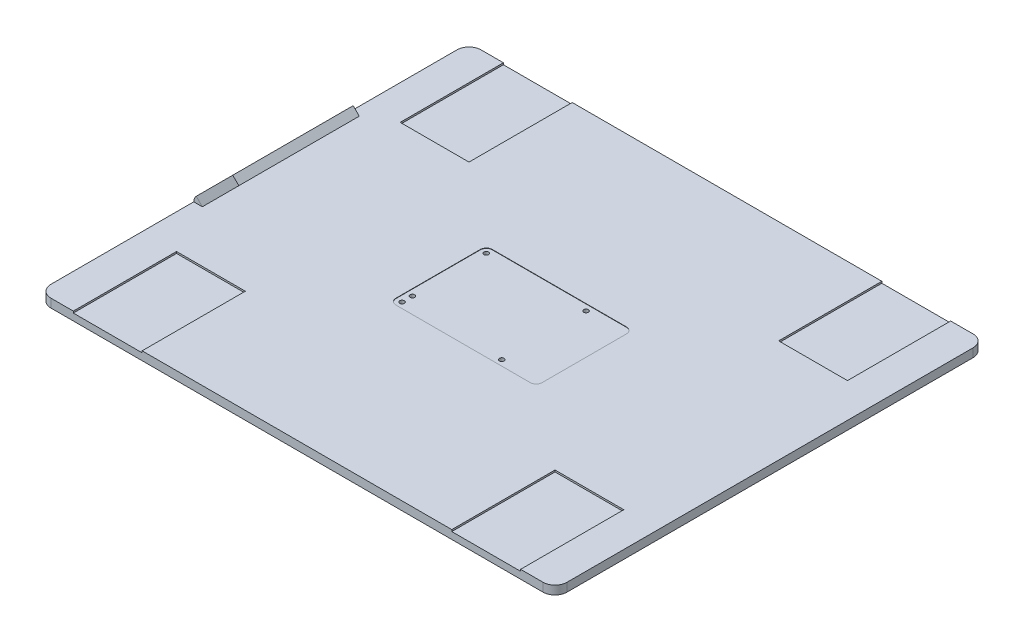
SolidWorks part; units mm, degrees
ref_plane "Front Plane" through (0, 0, 0) normal (0, 0, 1) x (1, 0, 0)
ref_plane "Top Plane" through (0, 0, 0) normal (0, 1, 0) x (1, 0, 0)
ref_plane "Right Plane" through (0, 0, 0) normal (1, 0, 0) x (0, 0, -1)
sketch "Sketch1" plane through (0, 0, 0) normal (0, 1, 0) x (1, 0, 0)
  line L0 (107.2728, -97.2075) -> (107.2728, -100.7075) construction
  line L1 (7, 0) -> (293, 0)
  line L2 (0, -7) -> (0, -243)
  line L3 (7, -250) -> (293, -250)
  line L4 (300, -7) -> (300, -243)
  line L5 (110.7728, -97.2075) -> (188.7728, -97.2075)
  line L6 (107.2728, -100.7075) -> (107.2728, -149.7075)
  line L7 (110.7728, -153.2075) -> (188.7728, -153.2075)
  line L8 (192.2728, -100.7075) -> (192.2728, -149.7075)
  line L9 (107.2728, -100.7075) -> (107.2728, -149.7075)
  line L10 (107.2728, -100.7075) -> (192.2728, -100.7075) construction
  line L11 (107.2728, -149.7075) -> (192.2728, -149.7075) construction
  line L12 (107.2728, -97.2075) -> (110.7728, -97.2075) construction
  line L13 (110.7728, -97.2075) -> (110.7728, -153.2075) construction
  line L14 (110.7728, -97.2075) -> (168.7728, -97.2075) construction
  line L15 (168.7728, -97.2075) -> (168.7728, -153.2075) construction
  line L16 (110.7728, -97.2075) -> (110.7728, -100.7075) construction
  line L17 (110.7728, -100.7075) -> (168.7728, -100.7075) construction
  line L18 (168.7728, -100.7075) -> (168.7728, -149.7075) construction
  line L19 (168.7728, -149.7075) -> (110.7728, -149.7075) construction
  line L20 (110.7728, -149.7075) -> (110.7728, -100.7075) construction
  line L21 (110.7728, -149.7075) -> (110.7728, -143.7075) construction
  line L22 (150, 0) -> (150, -250) construction
  line L23 (0, -125) -> (300, -125) construction
  line L24 (300, 0) -> (280, 0) construction
  line L25 (20, 0) -> (60, 0)
  line L26 (20, 0) -> (20, -60)
  line L27 (20, -60) -> (60, -60)
  line L28 (60, 0) -> (60, -60)
  line L29 (0, -250) -> (20, -250) construction
  line L30 (280, 0) -> (240, 0)
  line L31 (280, 0) -> (280, -60)
  line L32 (280, -60) -> (240, -60)
  line L33 (240, 0) -> (240, -60)
  line L34 (300, -250) -> (280, -250) construction
  line L36 (20, -250) -> (60, -250)
  line L37 (20, -250) -> (20, -190)
  line L38 (20, -190) -> (60, -190)
  line L39 (60, -250) -> (60, -190)
  line L40 (280, -250) -> (240, -250)
  line L41 (280, -250) -> (280, -190)
  line L42 (280, -190) -> (240, -190)
  line L43 (240, -250) -> (240, -190)
  circle A0 centre (110.7728, -100.7075) radius 1.35
  circle A1 centre (168.7728, -100.7075) radius 1.35
  circle A2 centre (168.7728, -149.7075) radius 1.35
  circle A3 centre (110.7728, -149.7075) radius 1.35
  arc A4 (110.7728, -97.2075) -> (107.2728, -100.7075) centre (110.7728, -100.7075) ccw
  arc A5 (107.2728, -149.7075) -> (110.7728, -153.2075) centre (110.7728, -149.7075) ccw
  arc A6 (188.7728, -153.2075) -> (192.2728, -149.7075) centre (188.7728, -149.7075) ccw
  arc A7 (188.7728, -97.2075) -> (192.2728, -100.7075) centre (188.7728, -100.7075) cw
  circle A8 centre (110.7728, -143.7075) radius 1.35
  arc A9 (0, -243) -> (7, -250) centre (7, -243) ccw
  arc A10 (293, -250) -> (300, -243) centre (293, -243) ccw
  arc A11 (293, 0) -> (300, -7) centre (293, -7) cw
  arc A12 (7, 0) -> (0, -7) centre (7, -7) ccw
  point P30 (107.2728, -153.2075)
  point P33 (192.2728, -153.2075)
  point P36 (192.2728, -97.2075)
  point P71 (0, 0)
  dimension "D10" = 2.7
  dimension "D11" = 2.7
  dimension "D12" = 2.7
  dimension "D13" = 2.7
  dimension "D14" = 3.5
  dimension "D15" = 3.5
  dimension "D16" = 2.7
  dimension "D21" = 7
  dimension "D1" = 300
  dimension "D2" = 250
  dimension "D3" = 85
  dimension "D4" = 56
  dimension "D5" = 3.5
  dimension "D6" = 49
  dimension "D7" = 3.5
  dimension "D8" = 3.5
  dimension "D9" = 58
  dimension "D17" = 6
  dimension "D18" = 20
  dimension "D19" = 60
  dimension "D20" = 40
extrude "Boss-Extrude1" add sketch "Sketch1" along normal blind 5 contours L4 L1 L2 L3 L5 A7 L8 A6 L7 A5 L6 A4 region at (13.5, 0, 3.9051)
extrude "Boss-Extrude2" add sketch "Sketch1<3>" along normal blind 4.8 contours A7 L5 A4 L6 A5 L7 A6 L8 A8 A3 A2 A1 A0 region at (149.8686, 0, 125.1851)
sketch "Sketch1<3>" plane through (0, 0, 0) normal (0, 1, 0) x (1, 0, 0) same geometry as "Sketch1"
extrude "Boss-Extrude3" add sketch "Sketch1<4>" along normal blind 4 contours L28 L1 L26 L27 | L1 L33 L32 L31 | L43 L3 L41 L42 | L3 L39 L38 L37 region at (40, 0, 30) region at (260, 0, 30) region at (40, 0, 220) region at (260, 0, 220)
sketch "Sketch1<4>" plane through (0, 0, 0) normal (0, 1, 0) x (1, 0, 0) same geometry as "Sketch1"
sketch "Sketch3" plane through (0, 5, 0) normal (0, 1, 0) x (1, 0, 0)
  line L0 (0, -125) -> (29.9772, -125) construction
  line L1 (0, -7) -> (0, -243) construction
  line L2 (0, -125) -> (5, -125) construction
  line L3 (5, -86.617) -> (5, -167.8751) construction
  line L5 (0, -125) -> (5, -125)
  line L6 (0, -125) -> (0, -105)
  line L7 (0, -105) -> (5, -105)
  line L8 (5, -125) -> (5, -105)
  line L9 (0, -125) -> (5, -125)
  line L10 (0, -125) -> (0, -145)
  line L11 (0, -145) -> (5, -145)
  line L12 (5, -125) -> (5, -145)
  line L13 (0, -105) -> (5, -105)
  line L14 (0, -105) -> (0, -90)
  line L15 (0, -90) -> (5, -90)
  line L16 (5, -105) -> (5, -90)
  line L17 (0, -145) -> (5, -145)
  line L18 (0, -145) -> (0, -160)
  line L19 (0, -160) -> (5, -160)
  line L20 (5, -145) -> (5, -160)
  dimension "D1" = 40
  dimension "D2" = 15
revolve "Revolve3" add sketch "Sketch3" angle 45 about L16 region at (2.5, 5, 97.5) region at (2.5, 5, 152.5) other way angle 45
sketch "Sketch6" plane through (5, 5, 0) normal (0.7071, 0.7071, 0) x (0, 0, -1)
  line L1 (-160, 5) -> (-90, 5)
  line L2 (-160, 5) -> (-160, 0)
  line L3 (-160, 0) -> (-90, 0)
  line L4 (-90, 5) -> (-90, 0)
extrude "Boss-Extrude6" add sketch "Sketch6" along normal blind 30 separate body
sketch "Sketch7" plane through (-3.5355, 3.5355, 0) normal (-0.7071, 0.7071, 0) x (0, 0, 1)
  line L0 (125, 37.0711) -> (125, 7.0711) construction
  line L1 (90, 37.0711) -> (160, 37.0711) construction
  line L2 (90, 7.0711) -> (160, 7.0711) construction
  line L3 (113, 7.0711) -> (113, 37.0711) construction
  line L4 (160, 7.0711) -> (90, 7.0711) construction
  line L5 (113, 7.0711) -> (113, 10.0711) construction
  line L7 (115.5, 10.0711) -> (135.5, 10.0711)
  line L8 (113, 12.5711) -> (113, 31.5711)
  line L9 (115.5, 34.0711) -> (135.5, 34.0711)
  line L10 (138, 12.5711) -> (138, 31.5711)
  arc A0 (113, 12.5711) -> (115.5, 10.0711) centre (115.5, 12.5711) ccw
  arc A1 (135.5, 10.0711) -> (138, 12.5711) centre (135.5, 12.5711) ccw
  arc A2 (135.5, 34.0711) -> (138, 31.5711) centre (135.5, 31.5711) cw
  arc A3 (113, 31.5711) -> (115.5, 34.0711) centre (115.5, 31.5711) cw
  circle A4 centre (115.5, 31.5711) radius 1.1
  circle A5 centre (135.5, 31.5711) radius 1.1
  circle A6 centre (115.5, 12.5711) radius 1.1
  circle A7 centre (135.5, 12.5711) radius 1.1
  point P19 (138, 10.0711)
  point P22 (138, 34.0711)
  point P25 (113, 34.0711)
  point P28 (115.5, 31.5711)
  point P31 (115.5, 31.5711)
  point P32 (0, 0)
  dimension "D5" = 2.5
  dimension "D1" = 12
  dimension "D2" = 25
  dimension "D3" = 3
  dimension "D4" = 24
extrude "Cut-Extrude1" cut sketch "Sketch7" against normal blind 0.2
extrude "Cut-Extrude2" cut sketch "Sketch7<8>" against normal blind 6 contours A6 | A7 | A5 | A4
sketch "Sketch7<8>" plane through (-3.5355, 3.5355, 0) normal (-0.7071, 0.7071, 0) x (0, 0, 1) same geometry as "Sketch7"
